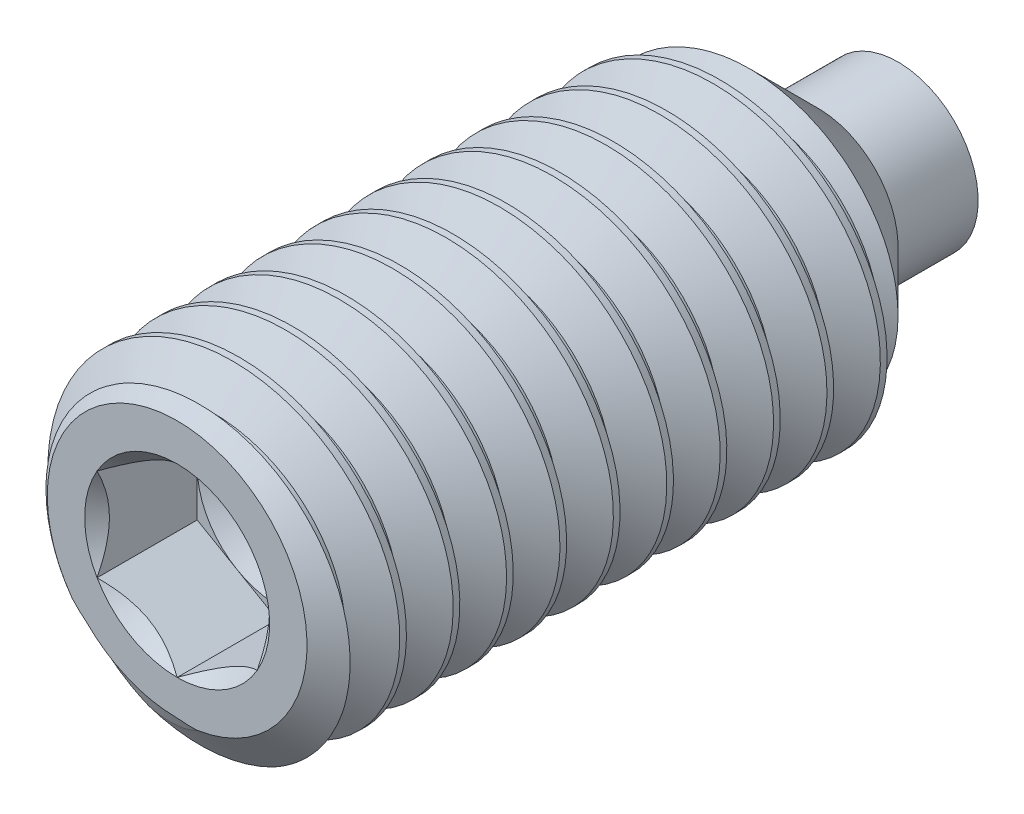
SolidWorks part; units mm, degrees
material "Plain Carbon Steel"
ref_plane "Front" through (0, 0, 0) normal (0, 0, 1) x (1, 0, 0)
ref_plane "Top" through (0, 0, 0) normal (0, 1, 0) x (1, 0, 0)
ref_plane "Right" through (0, 0, 0) normal (1, 0, 0) x (0, 0, -1)
sketch "Sketch22" plane through (0, 0, 0) normal (1, 0, 0) x (0, 0, -1)
  line L0 (-5.3578, 0) -> (-5.3578, 1.9304)
  line L1 (-5.3578, 1.9304) -> (-5.0199, 2.413)
  line L2 (-5.0199, 2.413) -> (2.9448, 2.413)
  line L3 (2.9448, 2.413) -> (4.1672, 1.1906)
  line L4 (-5.3578, 1.9304) -> (-5.3578, -1.9304) construction
  line L5 (5.3578, 0) -> (-5.3578, 0)
  line L6 (0, 2.413) -> (0, -2.413) construction
  line L8 (4.1672, 1.1906) -> (5.3578, 1.1906)
  line L9 (-3.9824, -2.413) -> (3.9824, -2.413) construction
  line L10 (5.3578, 1.1906) -> (5.3578, 0)
  line L11 (5.3578, 1.1906) -> (5.3578, -1.1906) construction
  dimension "D3" = 35
  dimension "D1" = 45
  dimension "Dia" = 4.826
  dimension "D2" = 3.8608
  dimension "A" = 2.3813
  dimension "B" = 1.1906
  dimension "Length" = 9.525
revolve "Revolve1" add sketch "Sketch22" angle 360 about L5
ref_plane "Plane1" through (0, 0, -4.1672) normal (0, 0, 1) x (1, 0, 0)
sketch "Sketch27" plane through (0, 0, -4.1672) normal (0, 0, 1) x (1, 0, 0)
  circle A0 centre (0, 0) radius 2.413 construction
  circle A1 centre (0, 0) radius 2.413
curve "Helix/Spiral1" pitch 0.7937 height 10.3188 radius 2.413 centre (0, 0, -4.1672) axis (0, 0, 1) start towards (0, 1, 0)
sketch "Sketch28" plane through (0, 0, 0) normal (1, 0, 0) x (0, 0, -1)
  line L0 (4.1672, 2.413) -> (4.8617, 2.413)
  line L1 (4.8617, 2.413) -> (4.5641, 1.8974)
  line L2 (4.5641, 1.8974) -> (4.4648, 1.8974)
  line L3 (4.4648, 1.8974) -> (4.1672, 2.413)
  line L4 (4.316, 2.1552) -> (4.7129, 2.1552) construction
  line L6 (-5.0199, 2.413) -> (2.9448, 2.413) construction
  line L7 (4.1672, 2.7075) -> (4.1672, -2.7075) construction
  dimension "D1" = 0.0992
  dimension "D3" = 60
  dimension "D2" = 0.3969
sweep "Cut-Sweep2" cut profiles "Sketch28" path "Helix/Spiral1" align with end faces yes
sketch "Sketch23" plane through (0, 0, 5.3578) normal (0, 0, 1) x (1, 0, 0)
  line L1 (0, 1.3748) -> (-1.1906, 0.6874)
  line L2 (-1.1906, 0.6874) -> (-1.1906, -0.6874)
  line L3 (-1.1906, -0.6874) -> (0, -1.3748)
  line L4 (0, -1.3748) -> (1.1906, -0.6874)
  line L5 (1.1906, -0.6874) -> (1.1906, 0.6874)
  line L6 (1.1906, 0.6874) -> (0, 1.3748)
  circle A0 centre (0, 0) radius 1.1906 construction
  dimension "Hex" = 2.3813
extrude "Cut-Extrude10" cut sketch "Sketch23" against normal blind 1.4883
sketch "Sketch24" plane through (0, 0, 5.3578) normal (0, 0, 1) x (1, 0, 0)
  circle A0 centre (0, 0) radius 1.3748
extrude "Cut-Extrude11" cut sketch "Sketch24" against normal through all draft 45
sketch "Sketch26" plane through (0, 0, 3.8695) normal (0, 0, 1) x (1, 0, 0)
  circle A0 centre (0, 0) radius 1.1906 construction
  circle A1 centre (0, 0) radius 1.1906
extrude "Cut-Extrude12" cut sketch "Sketch26" against normal through all draft 60
sketch "Sketch30" plane through (0, 0, 0) normal (1, 0, 0) x (0, 0, -1)
  line L0 (-5.0199, 2.413) -> (2.9448, 2.413) construction
  line L1 (-5.3578, 0) -> (-5.3578, 1.9304) construction
  line L2 (4.1672, 2.413) -> (4.1672, -2.413) construction
  line L3 (-3.9824, -2.413) -> (3.9824, -2.413) construction
  point P0 (-5.3578, 2.413)
  point P1 (5.3578, 2.413)
  point P2 (5.3578, -2.413)
  point P11 (1.3891, -2.413)
  dimension "D1" = 2.7781
equation "\"D1@Sketch28\" = \"D4@Helix/Spiral1\" * .125"
equation "\"D3@Helix/Spiral1\" = \"Length@Sketch22\" + \"D4@Helix/Spiral1\""
equation "\"D1@Sketch30\" = \"D4@Helix/Spiral1\" * 3.5"
equation "\"hex Depth@Cut-Extrude10\" = \"Hex@Sketch23\" * .625"
equation "\"D2@Sketch28\" = \"D4@Helix/Spiral1\" * .5"
equation "\"D2@Sketch22\" = \"Dia@Sketch22\" * .8"
